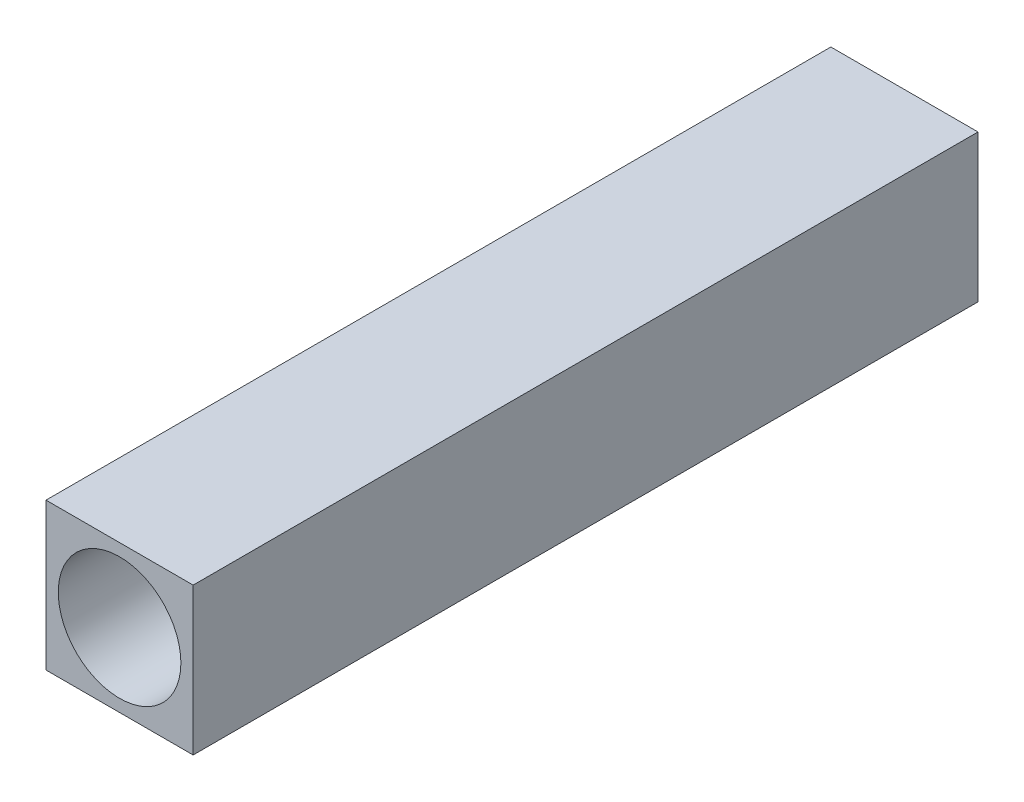
SolidWorks part; units mm, degrees
ref_plane "Front Plane" through (0, 0, 0) normal (0, 0, 1) x (1, 0, 0)
ref_plane "Top Plane" through (0, 0, 0) normal (0, 1, 0) x (1, 0, 0)
ref_plane "Right Plane" through (0, 0, 0) normal (1, 0, 0) x (0, 0, -1)
sketch "Sketch1" plane through (0, 0, 0) normal (0, 0, 1) x (1, 0, 0)
  line L1 (38.1, 38.1) -> (-38.1, 38.1)
  line L2 (38.1, 38.1) -> (38.1, -38.1)
  line L3 (38.1, -38.1) -> (-38.1, -38.1)
  line L4 (-38.1, 38.1) -> (-38.1, -38.1)
  line L5 (38.1, 38.1) -> (-38.1, -38.1) construction
  line L6 (38.1, -38.1) -> (-38.1, 38.1) construction
  circle A0 centre (0, 0) radius 31.75
  point P0 (0, 0)
  dimension "D1" = 63.5
  dimension "D3" = 76.2
extrude "Boss-Extrude1" add sketch "Sketch1" along normal blind 406.4 contours A0 | L1 L4 L3 L2 A0 region at (37.0224, 0, 0) region at (0, 0, 0)
extrude "Cut-Extrude1" cut sketch "Sketch1<3>" against normal blind 304.8 from surface contours A0 region at (0, 0, 0) starting at face at (0, 0, 406.4)
sketch "Sketch1<3>" plane through (0, 0, 0) normal (0, 0, 1) x (1, 0, 0) same geometry as "Sketch1"
